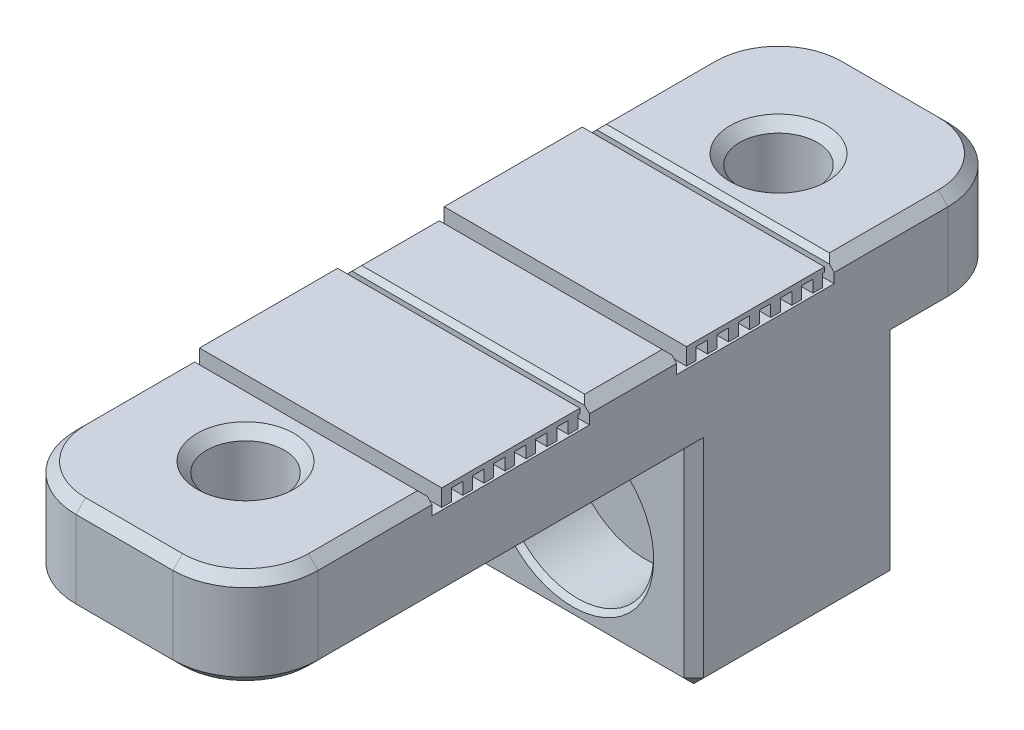
SolidWorks part; units mm, degrees
ref_plane "前视基准面" through (0, 0, 0) normal (0, 0, 1) x (1, 0, 0)
ref_plane "上视基准面" through (0, 0, 0) normal (0, 1, 0) x (1, 0, 0)
ref_plane "右视基准面" through (0, 0, 0) normal (1, 0, 0) x (0, 0, -1)
other "Configuration Table"
sketch "草图1" plane through (0, 0, 0) normal (0, 1, 0) x (1, 0, 0)
  line L1 (0, 0) -> (10, 0)
  line L2 (0, 0) -> (0, 32)
  line L3 (0, 32) -> (10, 32)
  line L4 (10, 0) -> (10, 32)
  circle A0 centre (5, 27) radius 1.6
  circle A1 centre (5, 5) radius 1.6
  point P7 (10, 16)
  dimension "D3" = 3.2
  dimension "D5" = 11
  dimension "D1" = 10
  dimension "D2" = 32
  dimension "D4" = 2
extrude "凸台-拉伸1" add sketch "草图1" along normal blind 4
sketch "草图2" plane through (0, 0, 0) normal (0, -1, 0) x (-1, 0, 0)
  line L0 (0, 32) -> (0, 0) construction
  line L1 (0, 18.5) -> (-10, 18.5)
  line L2 (0, 18.5) -> (0, 27)
  line L3 (0, 27) -> (-10, 27)
  line L4 (-10, 18.5) -> (-10, 27)
  line L5 (-10, 0) -> (-10, 32) construction
  circle A0 centre (-5, 27) radius 1.6 construction
  dimension "D1" = 8.5
  dimension "D2" = 0
extrude "凸台-拉伸2" add sketch "草图2" along normal blind 8.6
sketch "草图3" plane through (0, 0, -18.5) normal (0, 0, 1) x (1, 0, 0)
  line L0 (0, -8.6) -> (0, 0) construction
  line L3 (10, -8.6) -> (0, -8.6) construction
  circle A0 centre (5, -4.6) radius 3.15
  dimension "D1" = 6.3
  dimension "D3" = 4
  dimension "D2" = 5
extrude "切除-拉伸1" cut sketch "草图3" against normal blind 3
sketch "草图4" plane through (0, 0, 0) normal (0, -1, 0) x (-1, 0, 0)
  line L0 (0, 27) -> (-10, 27) construction
  circle A0 centre (-5, 27) radius 3
  dimension "D1" = 6
extrude "切除-拉伸2" cut sketch "草图4" along normal through all
sketch "草图5" plane through (0, 4, 0) normal (0, 1, 0) x (1, 0, 0)
  line L0 (0, 32) -> (0, 0) construction
  line L1 (0, 24.3) -> (10, 24.3)
  line L2 (0, 24.3) -> (0, 17.8)
  line L3 (0, 17.8) -> (10, 17.8)
  line L4 (10, 24.3) -> (10, 17.8)
  line L5 (10, 0) -> (10, 32) construction
  line L7 (0, 14.2) -> (10, 14.2)
  line L8 (0, 14.2) -> (0, 7.7)
  line L9 (0, 7.7) -> (10, 7.7)
  line L10 (10, 14.2) -> (10, 7.7)
  circle A0 centre (5, 27) radius 1.6 construction
  circle A1 centre (5, 5) radius 1.6 construction
  dimension "D1" = 2.7
  dimension "D2" = 2.7
  dimension "D3" = 6.5
  dimension "D4" = 6.5
extrude "切除-拉伸3" cut sketch "草图5" against normal blind 0.8
sketch "草图6" plane through (0, 4, 0) normal (0, 1, 0) x (1, 0, 0)
  line L0 (0, 14.2) -> (0, 7.7) construction
  line L1 (0, 13.8) -> (10, 13.8)
  line L2 (0, 13.8) -> (0, 8.1)
  line L3 (0, 8.1) -> (10, 8.1)
  line L4 (10, 13.8) -> (10, 8.1)
  line L5 (10, 7.7) -> (10, 14.2) construction
  line L6 (0, 24.3) -> (0, 17.8) construction
  line L7 (0, 23.9) -> (10, 23.9)
  line L8 (0, 23.9) -> (0, 18.2)
  line L9 (0, 18.2) -> (10, 18.2)
  line L10 (10, 23.9) -> (10, 18.2)
  line L11 (10, 24.3) -> (0, 24.3) construction
  line L13 (0, 17.8) -> (10, 17.8) construction
  line L14 (10, 14.2) -> (0, 14.2) construction
  line L15 (0, 7.7) -> (10, 7.7) construction
  dimension "D1" = 0.4
  dimension "D2" = 0.4
  dimension "D3" = 0.4
  dimension "D4" = 0.4
extrude "凸台-拉伸3" add sketch "草图6" against normal blind 0.2 separate body
sketch "草图7" plane through (0, 4, 0) normal (0, 1, 0) x (1, 0, 0)
  line L0 (10, 8.1) -> (10, 13.8) construction
  line L1 (0, 8.1) -> (10, 8.1)
  line L2 (0, 8.1) -> (0, 8.5)
  line L3 (0, 8.5) -> (10, 8.5)
  line L4 (10, 8.1) -> (10, 8.5)
  line L5 (10, 18.2) -> (10, 23.9) construction
  line L6 (0, 18.2) -> (10, 18.2)
  line L7 (0, 18.2) -> (0, 18.6)
  line L8 (0, 18.6) -> (10, 18.6)
  line L9 (10, 18.2) -> (10, 18.6)
  line L10 (0, 19.07) -> (0, 19.47)
  line L11 (0, 19.07) -> (10, 19.07)
  line L12 (10, 19.07) -> (10, 19.47)
  line L13 (0, 19.47) -> (10, 19.47)
  line L14 (0, 8.97) -> (0, 9.37)
  line L15 (0, 8.97) -> (10, 8.97)
  line L16 (10, 8.97) -> (10, 9.37)
  line L17 (0, 9.37) -> (10, 9.37)
  line L18 (0, 19.94) -> (0, 20.34)
  line L19 (0, 19.94) -> (10, 19.94)
  line L20 (10, 19.94) -> (10, 20.34)
  line L21 (0, 20.34) -> (10, 20.34)
  line L22 (0, 9.84) -> (0, 10.24)
  line L23 (0, 9.84) -> (10, 9.84)
  line L24 (10, 9.84) -> (10, 10.24)
  line L25 (0, 10.24) -> (10, 10.24)
  line L26 (0, 20.81) -> (0, 21.21)
  line L27 (0, 20.81) -> (10, 20.81)
  line L28 (10, 20.81) -> (10, 21.21)
  line L29 (0, 21.21) -> (10, 21.21)
  line L30 (0, 10.71) -> (0, 11.11)
  line L31 (0, 10.71) -> (10, 10.71)
  line L32 (10, 10.71) -> (10, 11.11)
  line L33 (0, 11.11) -> (10, 11.11)
  line L34 (0, 21.68) -> (0, 22.08)
  line L35 (0, 21.68) -> (10, 21.68)
  line L36 (10, 21.68) -> (10, 22.08)
  line L37 (0, 22.08) -> (10, 22.08)
  line L38 (0, 11.58) -> (0, 11.98)
  line L39 (0, 11.58) -> (10, 11.58)
  line L40 (10, 11.58) -> (10, 11.98)
  line L41 (0, 11.98) -> (10, 11.98)
  line L42 (0, 22.55) -> (0, 22.95)
  line L43 (0, 22.55) -> (10, 22.55)
  line L44 (10, 22.55) -> (10, 22.95)
  line L45 (0, 22.95) -> (10, 22.95)
  line L46 (0, 12.45) -> (0, 12.85)
  line L47 (0, 12.45) -> (10, 12.45)
  line L48 (10, 12.45) -> (10, 12.85)
  line L49 (0, 12.85) -> (10, 12.85)
  line L50 (0, 23.42) -> (0, 23.82)
  line L51 (0, 23.42) -> (10, 23.42)
  line L52 (10, 23.42) -> (10, 23.82)
  line L53 (0, 23.82) -> (10, 23.82)
  line L54 (0, 13.32) -> (0, 13.72)
  line L55 (0, 13.32) -> (10, 13.32)
  line L56 (10, 13.32) -> (10, 13.72)
  line L57 (0, 13.72) -> (10, 13.72)
  dimension "D1" = 0.4
  dimension "D2" = 0.4
  dimension "D3" = 7
extrude "凸台-拉伸4" add sketch "草图7" against normal blind 0.7
sketch "草图8" plane through (0, 0, 0) normal (0, -1, 0) x (-1, 0, 0)
  circle A0 centre (-5, 5) radius 3
  circle A1 centre (-5, 27) radius 3
  dimension "D1" = 6
  dimension "D2" = 6
extrude "切除-拉伸4" cut sketch "草图8" against normal blind 0.8
fillet "圆角1" radius 3 4 edges at (10, 2, 0) (0, 2, 0) (10, 2, -32) (0, 2, -32)
fillet "圆角3" radius 1 2 edges at (2, -4.3, -27) (8, -4.3, -27)
chamfer "倒角1" distance 0.2 angle 45 4 edges at (5, 4, -24.3) (5, 4, -17.8) (5, 4, -14.2) (5, 4, -7.7)
chamfer "倒角4" distance 0.4 angle 45 32 edges at (10, 4, -26.75) (0, 4, -26.75) (10, 4, -16) (0, 4, -16) (5, 4, -3.4) (0, 4, -5.25) (10, 4, -5.25) (0.8787, 4, -0.8787) (9.1213, 4, -0.8787) (5, 4, 0) (5, 4, -25.4) (5, 0, -8) (10, 0, -10.75) (9.1213, 0, -0.8787) (5, 0, 0) (0.8787, 0, -0.8787) (10, -4.3, -27) (0, 0, -10.75) (10, -4.3, -18.5) (10, -8.6, -22.75) (5, -8.6, -18.5) (0, -4.3, -18.5) (0, -8.6, -22.75) (0, -4.3, -27) (0, 0, -28) (10, 0, -28) (5, 0, -32) (5, 4, -32) (9.1213, 0, -31.1213) (0.8787, 0, -31.1213) (9.1213, 4, -31.1213) (0.8787, 4, -31.1213)
chamfer "倒角6" distance 0.2 angle 45 1 edges at (8.15, -4.6, -18.5)
